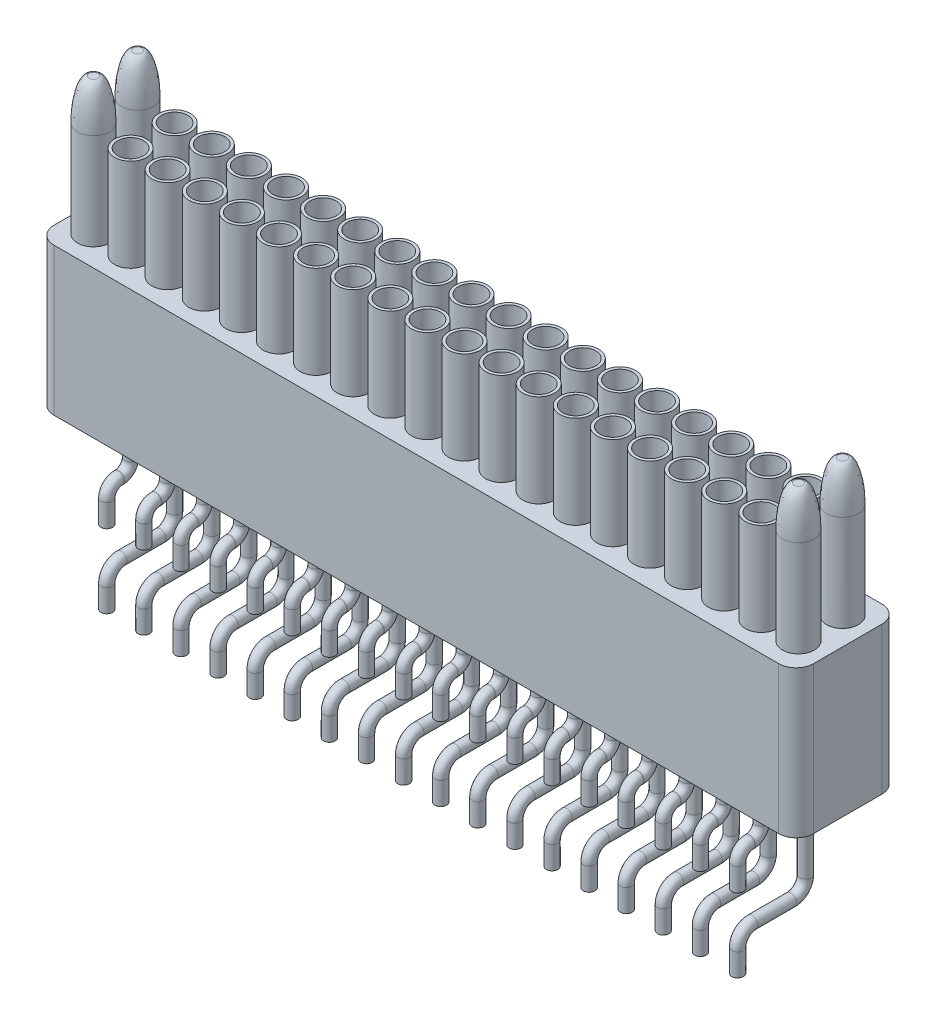
SolidWorks part; units mm, degrees
ref_plane "Front Plane" through (0, 0, 0) normal (0, 0, 1) x (1, 0, 0)
ref_plane "Top Plane" through (0, 0, 0) normal (0, 1, 0) x (1, 0, 0)
ref_plane "Right Plane" through (0, 0, 0) normal (1, 0, 0) x (0, 0, -1)
sketch "Sketch1" plane through (0, 0, 0) normal (0, 0, 1) x (1, 0, 0)
  line L1 (-6.55, -1.27) -> (6.55, -1.27)
  line L2 (-6.55, -1.27) -> (-6.55, 1.27)
  line L3 (-6.55, 1.27) -> (6.55, 1.27)
  line L4 (6.55, -1.27) -> (6.55, 1.27)
  line L5 (-6.55, -1.27) -> (6.55, 1.27) construction
  line L6 (-6.55, 1.27) -> (6.55, -1.27) construction
  point P0 (0, 0)
  dimension "D1" = 13.1
  dimension "D2" = 2.54
extrude "Boss-Extrude1" add sketch "Sketch1" along normal blind 1.78 contours L3 L4 L1 L2
sketch "Sketch2" plane through (0, 1.27, 0) normal (0, 1, 0) x (1, 0, 0)
  line L0 (-6.55, -0.89) -> (6.55, -0.89) construction
  line L1 (-6.55, -1.78) -> (-6.55, 0) construction
  line L2 (6.55, -1.78) -> (6.55, 0) construction
  line L3 (0, 0) -> (0, -1.78) construction
  line L4 (-6.55, -1.78) -> (6.55, -1.78) construction
  circle A0 centre (-0.32, -0.51) radius 0.275
  circle A1 centre (-0.32, -0.51) radius 0.225
  dimension "D3" = 0.55
  dimension "D4" = 0.05
  dimension "D1" = 0.38
  dimension "D2" = 0.32
extrude "Boss-Extrude2" add sketch "Sketch2" along normal blind 1.6
pattern_linear "LPattern1" count 10 spacing 0.64 along (1, 0, 0) count 2 spacing 0.76 along (0, 0, 1) of "Boss-Extrude2"
pattern_linear "LPattern2" count 9 spacing 0.64 along (-1, 0, 0) count 2 spacing 0.76 along (0, 0, 1) of "Boss-Extrude2"
ref_point "Point1"
ref_plane "Plane1" through (-5.44, 0, 0) normal (-1, 0, 0) x (0, 0, 1)
sketch "Sketch3" plane through (-5.44, 0, 0) normal (-1, 0, 0) x (0, 0, 1)
  line L0 (0.51, -1.27) -> (0.51, -2.92)
  line L1 (1.78, -1.27) -> (0, -1.27) construction
  line L2 (0.76, -3.17) -> (1.43, -3.17)
  line L3 (1.68, -3.42) -> (1.68, -3.81)
  line L4 (1.78, 1.27) -> (0, 1.27) construction
  line L6 (1.78, -1.27) -> (1.78, 1.27) construction
  arc A0 (1.43, -3.17) -> (1.68, -3.42) centre (1.43, -3.42) cw
  arc A1 (0.51, -2.92) -> (0.76, -3.17) centre (0.76, -2.92) ccw
  point P13 (1.68, -3.17)
  dimension "D4" = 0.25
  dimension "D1" = 0.64
  dimension "D2" = 5.08
  dimension "D3" = 0.1
sketch "Sketch4" plane through (0, -1.27, 0) normal (0, -1, 0) x (1, 0, 0)
  circle A0 centre (-5.44, 0.51) radius 0.1
  dimension "D1" = 0.2
sweep "Sweep2" add profiles "Sketch4" path "Sketch3"
ref_point "Point3"
sketch "Sketch6" plane through (-5.44, 0, 0) normal (-1, 0, 0) x (0, 0, 1)
  line L0 (1.2713, -1.27) -> (1.2713, -1.7482)
  line L1 (1.78, -1.27) -> (0, -1.27) construction
  line L2 (1.4713, -1.9482) -> (1.48, -1.9482)
  line L3 (1.68, -2.1482) -> (1.68, -2.54)
  line L4 (1.78, 1.27) -> (0, 1.27) construction
  arc A0 (1.48, -1.9482) -> (1.68, -2.1482) centre (1.48, -2.1482) cw
  arc A1 (1.2713, -1.7482) -> (1.4713, -1.9482) centre (1.4713, -1.7482) ccw
  dimension "D2" = 0.2
  dimension "D1" = 3.81
sketch "Sketch7" plane through (0, -1.27, 0) normal (0, -1, 0) x (-1, 0, 0)
  circle A0 centre (5.44, -1.2713) radius 0.1
  dimension "D1" = 0.2
sweep "Sweep3" add profiles "Sketch7" path "Sketch6"
pattern_linear "LPattern3" count 18 spacing 0.64 along (1, 0, 0) of "Sweep2", "Sweep3"
sketch "Sketch8" plane through (0, 1.27, 0) normal (0, 1, 0) x (1, 0, 0)
  line L0 (5.44, -0.51) -> (6.55, -0.51) construction
  line L1 (6.55, -1.78) -> (6.55, 0) construction
  circle A0 centre (6.08, -0.51) radius 0.275
  point P7 (0, 0)
  point P8 (6.0993, -0.51)
  dimension "D2" = 0.55
  dimension "D1" = 0.64
extrude "Boss-Extrude3" add sketch "Sketch8" along normal blind 2.36 contours A0
fillet "Fillet1" radius 0.7 1 edges at (6.08, 3.63, 0.785) second distance 0.2 first distance on face at (6.08, 3.63, 0.785)
pattern_linear "LPattern5" count 2 spacing 12.16 along (-1, 0, 0) count 2 spacing 0.76 along (0, 0, 1) of "Fillet1", "Boss-Extrude3"
fillet "Fillet2" radius 0.3 4 edges at (6.55, 0, 1.78) (-6.55, 0, 1.78) (6.55, 0, 0) (-6.55, 0, 0)
